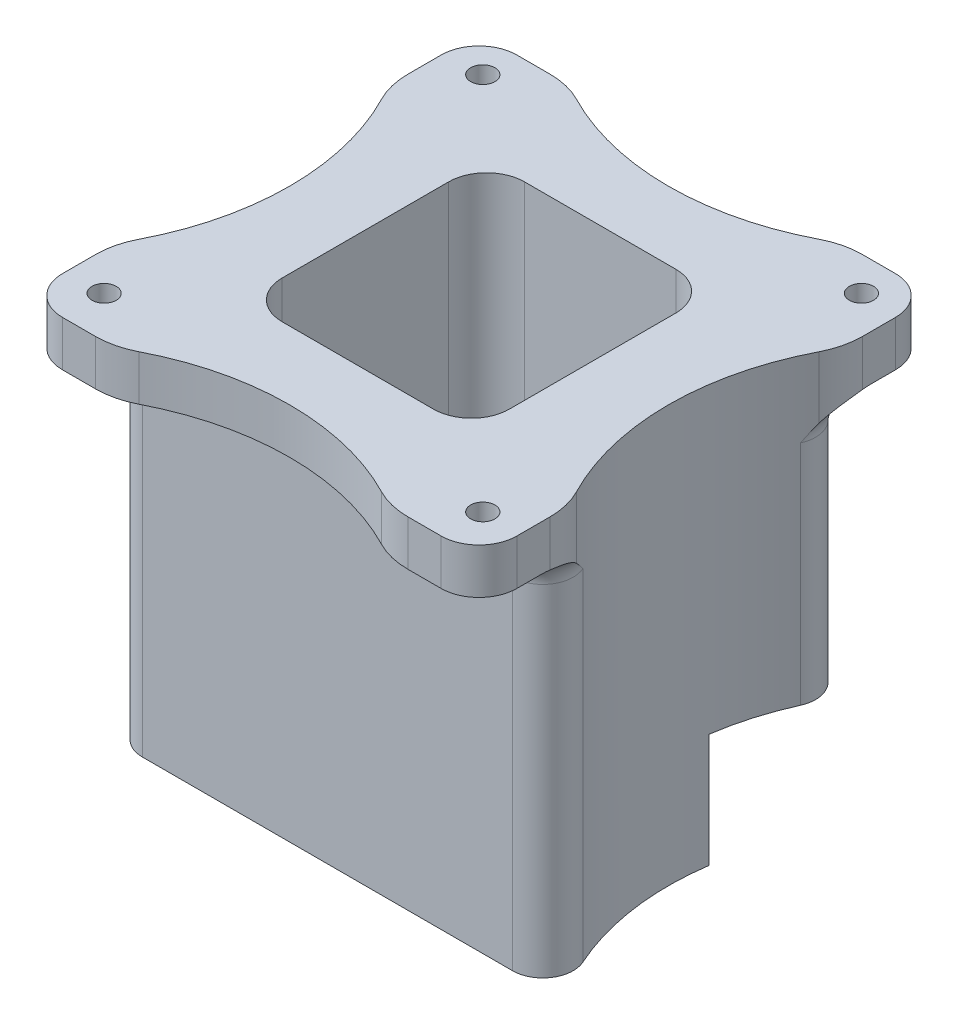
SolidWorks part; units mm, degrees
material "PLA"
ref_plane "前视基准面" through (0, 0, 0) normal (0, 0, 1) x (1, 0, 0)
ref_plane "上视基准面" through (0, 0, 0) normal (0, 1, 0) x (1, 0, 0)
ref_plane "右视基准面" through (0, 0, 0) normal (1, 0, 0) x (0, 0, -1)
sketch "草图1" plane through (0, 0, 0) normal (1, 0, 0) x (0, 0, -1)
  line L0 (-25, 0) -> (0, 0)
  line L1 (0, 0) -> (0, 15)
  line L2 (0, 15) -> (15, 15)
  line L3 (25, 49) -> (25, 55)
  line L4 (25, 55) -> (-35, 55)
  line L5 (-35, 55) -> (-35, 49)
  line L6 (15, 15) -> (15, 49)
  line L7 (15, 49) -> (25, 49)
  line L8 (-35, 49) -> (-25, 49)
  line L9 (-25, 49) -> (-25, 0)
  dimension "D1" = 35
  dimension "D2" = 25
  dimension "D3" = 15
  dimension "D4" = 55
  dimension "D5" = 15
  dimension "D6" = 6
  dimension "D7" = 25
extrude "凸台-拉伸1" add sketch "草图1" along normal blind 60
sketch "草图2" plane through (0, 55, 0) normal (0, 1, 0) x (1, 0, 0)
  line L0 (60, -35) -> (0, -35) construction
  line L1 (5, 20.5) -> (55, 20.5) construction
  line L2 (5, 20.5) -> (5, -29.5) construction
  line L3 (5, -29.5) -> (55, -29.5) construction
  line L4 (55, 20.5) -> (55, -29.5) construction
  line L5 (60, 0) -> (0, 0) construction
  circle A0 centre (55, 20.5) radius 1.6
  circle A1 centre (5, 20.5) radius 1.6
  circle A2 centre (5, -29.5) radius 1.6
  circle A3 centre (55, -29.5) radius 1.6
  point P4 (30, -29.5)
  point P7 (30, -35)
  dimension "D2" = 3.2
  dimension "D1" = 50
  dimension "D3" = 29.5
extrude "切除-拉伸1" cut sketch "草图2" against normal blind 10
fillet "圆角1" radius 5 4 edges at (0, 52, -25) (0, 52, 35) (60, 52, -25) (60, 52, 35)
sketch "草图4" plane through (0, 0, 0) normal (0, 0, -1) x (-1, 0, 0)
  line L0 (-60, 7.5) -> (0, 7.5) construction
  line L1 (-60, 0) -> (-60, 15) construction
  line L2 (0, 0) -> (0, 15) construction
  line L3 (-30, 0) -> (-30, 15) construction
  line L4 (-60, 0) -> (0, 0) construction
  line L5 (-60, 15) -> (0, 15) construction
  circle A0 centre (-10, 7.5) radius 1.4
  circle A1 centre (-50, 7.5) radius 1.4
  dimension "D1" = 40
  dimension "D2" = 2.8
extrude "切除-拉伸2" cut sketch "草图4" against normal blind 10
sketch "草图6" plane through (0, 55, 0) normal (0, 1, 0) x (1, 0, 0)
  line L0 (-30, -5) -> (90, -5) construction
  line L1 (30, 55) -> (30, -65) construction
  line L2 (55, -35) -> (5, -35) construction
  line L3 (60, 20) -> (60, -30) construction
  line L5 (15, -21) -> (45, -21)
  line L6 (15, -21) -> (15, 11)
  line L7 (15, 11) -> (45, 11)
  line L8 (45, -21) -> (45, 11)
  line L9 (15, -21) -> (45, 11) construction
  line L10 (15, 11) -> (45, -21) construction
  circle A0 centre (-30, -5) radius 35
  circle A1 centre (90, -5) radius 35
  circle A2 centre (30, 55) radius 35
  circle A3 centre (30, -65) radius 35
  point P8 (30, -5)
  point P11 (30, -35)
  point P14 (60, -5)
  point P15 (30, -5)
  dimension "D1" = 70
  dimension "D3" = 70
  dimension "D2" = 120
  dimension "D4" = 120
  dimension "D5" = 32
  dimension "D6" = 30
extrude "切除-拉伸4" cut sketch "草图6" against normal through all
fillet "圆角2" radius 10 8 edges at (48.0278, 52, -25) (11.9722, 52, -25) (0, 35, -13.0278) (0, 27.5, 23.0278) (60, 35, -13.0278) (60, 27.5, 23.0278) (11.9722, 52, 35) (48.0278, 52, 35)
fillet "圆角3" radius 5 4 edges at (15, 27.5, 21) (45, 27.5, 21) (45, 35, -11) (15, 35, -11)
fillet "圆角4" radius 4 4 edges at (0.019, 32, -15) (59.981, 32, -15) (0.019, 24.5, 25) (59.981, 24.5, 25)
fillet "圆角5" radius 4 6 edges at (57.792, 49, -13.1721) (2.208, 49, -13.1721) (57.792, 49, 23.1721) (2.208, 49, 23.1721) (30, 49, -15) (30, 49, 25)
sketch "草图7" plane through (0, 0, 0) normal (0, -1, 0) x (1, 0, 0)
  line L0 (10, 18) -> (50, 18) construction
  line L1 (15, 0) -> (45, 0) construction
  circle A0 centre (10, 18) radius 1.4
  circle A1 centre (50, 18) radius 1.4
  point P6 (30, 0)
  point P7 (30, 18)
  dimension "D3" = 2.8
  dimension "D1" = 18
  dimension "D2" = 40
extrude "切除-拉伸5" cut sketch "草图7" against normal blind 10
chamfer "倒角1" distance 0.5 angle 45 4 edges at (8.6, 7.5, 0) (48.6, 7.5, 0) (10, 0, 16.6) (50, 0, 16.6)
sketch "草图8" plane through (0, 15, 0) normal (0, -1, 0) x (1, 0, 0)
  line L0 (40, -11) -> (20, -11) construction
  line L1 (24, -11) -> (36, -11)
  line L2 (24, -11) -> (24, -15)
  line L3 (24, -15) -> (36, -15)
  line L4 (36, -11) -> (36, -15)
  line L5 (5.5668, -15) -> (54.4332, -15) construction
  line L6 (20, 21) -> (40, 21) construction
  point P8 (30, -11)
  point P11 (30, 21)
  dimension "D1" = 12
extrude "切除-拉伸6" cut sketch "草图8" against normal blind 10
